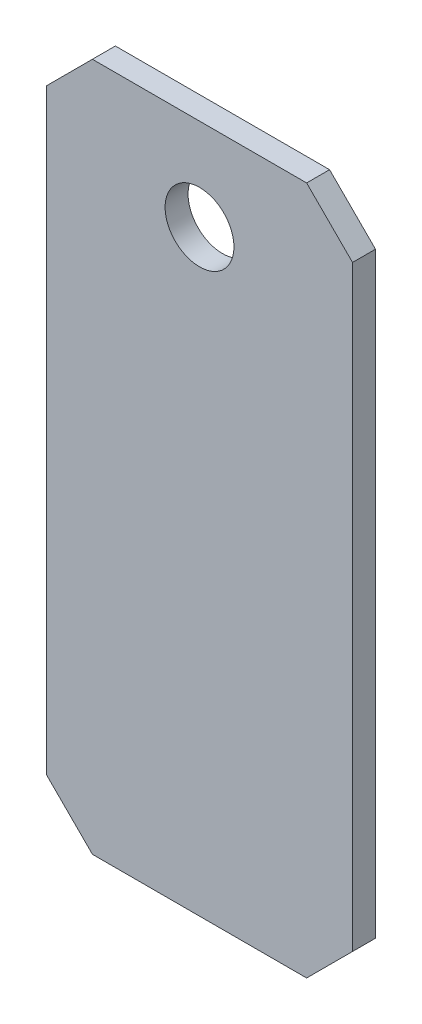
SolidWorks part; units mm, degrees
material "Acrylic"
ref_plane "Front Plane" through (0, 0, 0) normal (0, 0, 1) x (1, 0, 0)
ref_plane "Top Plane" through (0, 0, 0) normal (0, 1, 0) x (1, 0, 0)
ref_plane "Right Plane" through (0, 0, 0) normal (1, 0, 0) x (0, 0, -1)
sketch "Sketch1" plane through (0, 0, 0) normal (0, 0, 1) x (1, 0, 0)
  line L0 (-7, 22.5) -> (-10, 19.5)
  line L1 (7, -22.5) -> (-7, -22.5)
  line L2 (10, -19.5) -> (10, 19.5)
  line L3 (7, 22.5) -> (-7, 22.5)
  line L4 (-10, -19.5) -> (-10, 19.5)
  line L5 (10, -22.5) -> (-10, 22.5) construction
  line L6 (10, 22.5) -> (-10, -22.5) construction
  line L7 (10, 19.5) -> (7, 22.5)
  line L8 (-7, -22.5) -> (-10, -19.5)
  line L9 (10, -19.5) -> (7, -22.5)
  circle A0 centre (0, 16.5) radius 2.25
  point P0 (0, 0)
  dimension "D3" = 4.5
  dimension "D1" = 20
  dimension "D2" = 45
  dimension "D4" = 6
extrude "Base" add sketch "Sketch1" along normal mid plane 1.5
sketch "Sketch2" [suppressed] plane through (0, 0, 0.75) normal (0, 0, 1) x (1, 0, 0)
  text T0 "<b><r90>X</r></b>" font "Open Sans" height in points 36
extrude "Text-X" [suppressed] add sketch "Sketch2" along normal blind 0.1
sketch "Sketch3" [suppressed] plane through (0, 0, 0.75) normal (0, 0, 1) x (1, 0, 0)
  text T0 "<b><r90>Y</r></b>" font "Open Sans" height in points 36
extrude "Text-Y" [suppressed] add sketch "Sketch3" along normal blind 0.1
sketch "Sketch4" [suppressed] plane through (0, 0, 0.75) normal (0, 0, 1) x (1, 0, 0)
  text T0 "<b><r90>Z</r></b>" font "Open Sans" height in points 36
extrude "Text-Z" [suppressed] add sketch "Sketch4" along normal blind 0.1
sketch "Sketch5" plane through (0, 0, 0.75) normal (0, 0, 1) x (1, 0, 0)
sketch_block_instance "Block3-1"
sketch_block "Block3"
extrude "Text-DATA" [suppressed] add sketch "Sketch5" along normal blind 0.1
sketch "Sketch6" plane through (0, 0, 0.75) normal (0, 0, 1) x (1, 0, 0)
sketch_block_instance "Block2-2"
sketch_block "Block2"
extrude "Text-PWR" [suppressed] add sketch "Sketch6" along normal blind 0.1
sketch "Sketch7" plane through (0, 0, 0.75) normal (0, 0, 1) x (1, 0, 0)
  line L0 (-7, -22.5) -> (7, -22.5) construction
  line L1 (6.25, -21.3) -> (-6.25, -21.3) construction
  line L2 (6.25, -21.3) -> (6.25, 13.2) construction
  line L3 (6.25, 13.2) -> (-6.25, 13.2) construction
  line L4 (-6.25, -21.3) -> (-6.25, 13.2) construction
  line L5 (0, 0) -> (0, 2.7854) construction
  dimension "D1" = 12.5
  dimension "D2" = 1.2
  dimension "D3" = 34.5
